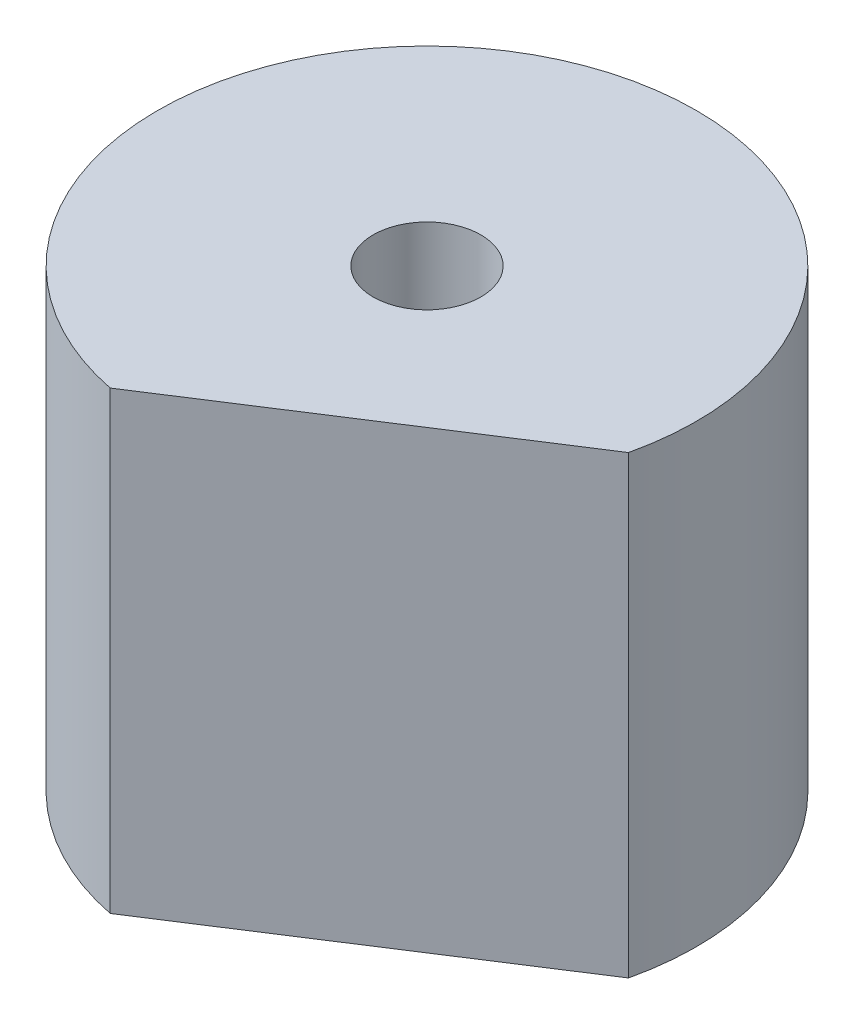
SolidWorks part; units mm, degrees
material "Oak"
ref_plane "Front" through (0, 0, 0) normal (0, 0, 1) x (1, 0, 0)
ref_plane "Top" through (0, 0, 0) normal (0, 1, 0) x (1, 0, 0)
ref_plane "Right" through (0, 0, 0) normal (1, 0, 0) x (0, 0, -1)
ref_axis "side-side" through (80.9, 0, 0) along (-1, 0, 0)
ref_axis "up-down" through (0, 50, 0) along (0, -1, 0)
ref_axis "front-back" through (0, 0, -80.9) along (0, 0, 1)
sketch "Sketch1" plane through (0, 0, 0) normal (0, 1, 0) x (1, 0, 0)
  circle A0 centre (0, 0) radius 7.9375
  circle A1 centre (0, 0) radius 1.5875
  dimension "D1" = 3.175
  dimension "D2" = 15.875
extrude "Boss-Extrude1" add sketch "Sketch1" along normal blind 13.4112
sketch "Sketch2" plane through (0, 0, 0) normal (0, -1, 0) x (1, 0, 0)
  line L1 (8.8489, 1.0735) -> (-2.6678, 8.5052)
  line L2 (0, 0) -> (3.0905, 4.7893) construction
extrude "Cut-Extrude1" cut sketch "Sketch2" against normal through all both and the other way through all flip side to cut
